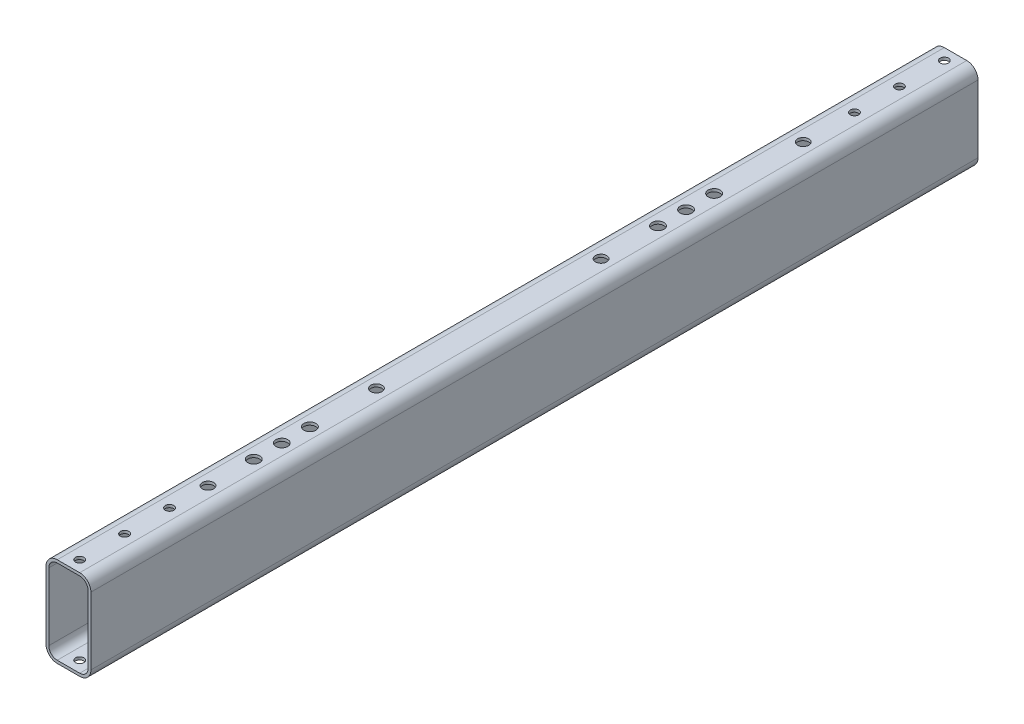
SolidWorks part; units mm, degrees
material "6061-T6 (SS)"
ref_plane "Front Plane" through (0, 0, 0) normal (0, 0, 1) x (1, 0, 0)
ref_plane "Top Plane" through (0, 0, 0) normal (0, 1, 0) x (1, 0, 0)
ref_plane "Right Plane" through (0, 0, 0) normal (1, 0, 0) x (0, 0, -1)
sketch "Sketch1" plane through (0, 0, 0) normal (0, 0, 1) x (1, 0, 0)
  line L1 (-6.35, -25.4) -> (6.35, -25.4)
  line L2 (-12.7, -19.05) -> (-12.7, 19.05)
  line L3 (-6.35, 25.4) -> (6.35, 25.4)
  line L4 (12.7, -19.05) -> (12.7, 19.05)
  line L5 (-12.7, -25.4) -> (12.7, 25.4) construction
  line L6 (-12.7, 25.4) -> (12.7, -25.4) construction
  arc A0 (-12.7, -19.05) -> (-6.35, -25.4) centre (-6.35, -19.05) ccw
  arc A1 (6.35, -25.4) -> (12.7, -19.05) centre (6.35, -19.05) ccw
  arc A2 (6.35, 25.4) -> (12.7, 19.05) centre (6.35, 19.05) cw
  arc A3 (-12.7, 19.05) -> (-6.35, 25.4) centre (-6.35, 19.05) cw
  point P0 (0, 0)
  dimension "D3" = 6.35
  dimension "D1" = 50.8
  dimension "D2" = 25.4
extrude "Extrude-Thin1" add sketch "Sketch1" along normal blind 501.65 thin thin type one direction reverse wall 1.5875
hole_wizard "3/16 (0.1875) Diameter Hole1" positions "3DSketch1" profile "Sketch3" hole size "3/16" standard "ANSI Inch" end condition through all
sketch3d "3DSketch1"
  line L1 (6.35, 25.4, 0) -> (-6.35, 25.4, 0) construction
  line L6 (0, 25.4, 501.65) -> (0, 25.4, 0) construction
  line L7 (6.35, 25.4, 501.65) -> (-6.35, 25.4, 501.65) construction
  point P57 (0, 25.4, 6.35)
  point P59 (0, 25.4, 31.75)
  point P61 (0, 25.4, 57.15)
  point P63 (0, 25.4, 469.9)
  point P65 (0, 25.4, 444.5)
  point P67 (0, 25.4, 495.3)
  dimension "D1" = 25.4
  dimension "D2" = 25.4
  dimension "D3" = 6.35
  dimension "D4" = 25.4
  dimension "D5" = 25.4
  dimension "D6" = 6.35
sketch "Sketch3" plane through (0, 25.4, 495.3) normal (1, 0, 0) x (0, 0, 1)
  line L0 (0, 0) -> (0, 50.8)
  line L1 (0, 50.8) -> (2.3812, 50.8)
  line L2 (2.3812, 50.8) -> (2.3812, 0)
  line L5 (2.3812, 0) -> (0, 0)
  line L11 (0, -6.35) -> (0, 107.95) construction
  dimension "Thru Hole Dia." = 4.7625
  dimension "Thru Hole Depth" = 50.8
hole_wizard "3/16 (0.195) Diameter Hole1" positions "Sketch4" profile "Sketch5" hole size "3/16" standard "ANSI Inch" end condition up to next
sketch "Sketch4" plane through (0, -25.4, 0) normal (0, -1, 0) x (-1, 0, 0)
  point P74 (-3.175, -85.7193)
  point P78 (3.175, -111.1193)
  point P81 (-3.175, -136.5193)
  point P84 (3.175, -161.9193)
  point P87 (-3.175, -187.3193)
  point P90 (3.175, -212.7193)
  point P93 (-3.175, -238.1193)
  point P96 (3.175, -263.5193)
  point P99 (-3.175, -288.9193)
  point P102 (3.175, -314.3193)
  point P105 (-3.175, -339.7193)
  point P108 (3.175, -365.1193)
  point P111 (3.175, -415.9193)
  point P114 (-3.175, -390.5193)
sketch "Sketch5" plane through (3.175, -25.4, 85.7193) normal (1, 0, 0) x (0, 0, -1)
  line L0 (0, 0) -> (0, 1.5875)
  line L1 (0, 1.5875) -> (2.4765, 1.5875)
  line L2 (2.4765, 1.5875) -> (2.4765, 0)
  line L5 (2.4765, 0) -> (0, 0)
  line L11 (0, -6.35) -> (0, 107.95) construction
  dimension "Thru Hole Dia." = 4.953
  dimension "Thru Hole Depth" = 1.5875
hole_wizard "1/4 (0.25) Diameter Hole1" positions "Sketch6" profile "Sketch7" hole size "1/4" standard "ANSI Inch"
sketch "Sketch6" plane through (0, 25.4, 0) normal (0, 1, 0) x (1, 0, 0)
  point P0 (0, -200.4645)
  point P15 (0, -422.731)
  point P23 (0, -327.481)
  point P26 (0, -86.1545)
sketch "Sketch7" plane through (0, 25.4, 200.4645) normal (1, 0, 0) x (0, 0, 1)
  line L0 (0, 0) -> (0, 27.3077)
  line L1 (0, 27.3077) -> (3.175, 25.4)
  line L2 (3.175, 25.4) -> (3.175, 0)
  line L5 (3.175, 0) -> (0, 0)
  line L10 (0, 27.3077) -> (-3.175, 25.4) construction
  line L11 (0, -6.35) -> (0, 107.95) construction
  dimension "Hole Dia." = 6.35
  dimension "Hole Depth" = 25.4
  dimension "Drill Angle" = 118
hole_wizard "1/4 Clearance Hole1" positions "Sketch17" profile "Sketch18" hole size "1/4" standard "ANSI Inch"
sketch "Sketch17" plane through (-381, 25.4, 250.825) normal (0, 1, 0) x (1, 0, 0)
  point P0 (381, 82.55)
  point P3 (381, 98.425)
  point P6 (381, 114.3)
  point P9 (381, -146.05)
  point P12 (381, -130.175)
  point P15 (381, -114.3)
  point P18 (-381, -146.05)
  point P21 (-381, -130.175)
  point P24 (-381, -114.3)
  point P27 (-381, 82.55)
  point P30 (-381, 98.425)
  point P33 (-381, 114.3)
sketch "Sketch18" plane through (0, 25.4, 168.275) normal (1, 0, 0) x (0, 0, 1)
  line L0 (0, 0) -> (0, 8.3798)
  line L1 (0, 8.3798) -> (3.3782, 6.35)
  line L2 (3.3782, 6.35) -> (3.3782, 0)
  line L3 (3.3782, 0) -> (0, 0)
  line L4 (0, 8.3798) -> (-3.3782, 6.35) construction
  line L5 (0, -6.35) -> (0, 107.95) construction
  dimension "Hole Dia." = 6.7564
  dimension "Hole Depth" = 6.35
  dimension "Drill Angle" = 118
